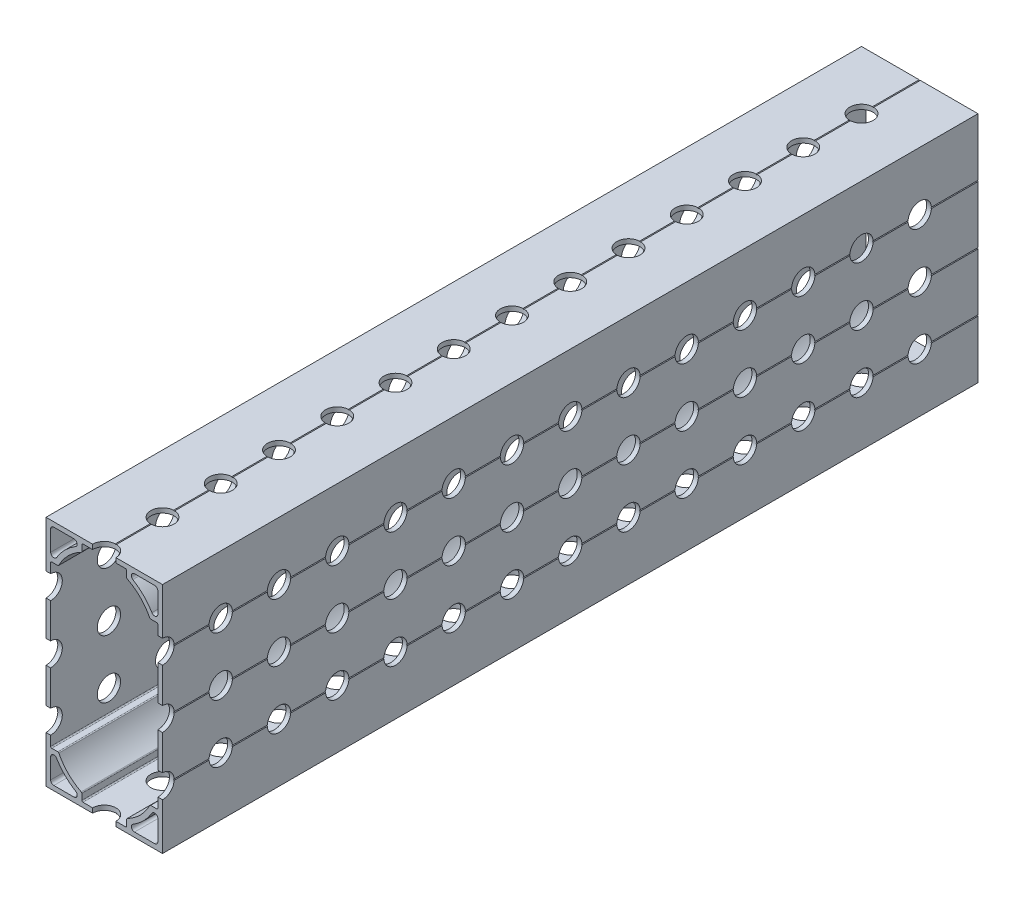
SolidWorks part; units mm, degrees
material "6061 Alloy"
ref_plane "Front Plane" through (0, 0, 0) normal (0, 0, 1) x (1, 0, 0)
ref_plane "Top Plane" through (0, 0, 0) normal (0, 1, 0) x (1, 0, 0)
ref_plane "Right Plane" through (0, 0, 0) normal (1, 0, 0) x (0, 0, -1)
other "Configuration Table"
sketch "Sketch3" plane through (0, 0, 0) normal (0, 0, 1) x (1, 0, 0)
  line L0 (0, 12.7) -> (0, -12.7) construction
  line L1 (12.7, -25.4) -> (0.127, -25.4)
  line L2 (12.7, -12.827) -> (12.7, -25.4)
  line L3 (12.573, -12.7) -> (12.7, -12.827)
  line L4 (-10.9924, -24.384) -> (-6.5971, -24.384)
  line L5 (-11.684, -19.2971) -> (-11.684, -23.6924)
  line L6 (12.7, -12.573) -> (12.573, -12.7)
  line L7 (12.7, -0.127) -> (12.7, -12.573)
  line L10 (12.573, 0) -> (12.7, -0.127)
  line L11 (0.127, -25.4) -> (0, -25.273)
  line L14 (11.684, 0) -> (11.684, -17.5895)
  line L15 (11.684, -17.5895) -> (9.979, -17.5895)
  line L18 (4.8895, -22.679) -> (4.8895, -24.384)
  line L19 (11.684, -19.2971) -> (11.684, -23.6924)
  line L20 (10.9924, -24.384) -> (6.5971, -24.384)
  line L21 (55, 0) -> (-55, 0) construction
  line L37 (12.573, 0) -> (12.7, 0.127)
  line L46 (-4.8895, -24.384) -> (4.8895, -24.384)
  line L47 (-4.8895, -22.679) -> (-4.8895, -24.384)
  line L48 (-11.684, -17.5895) -> (-9.979, -17.5895)
  line L49 (-11.684, 0) -> (-11.684, -17.5895)
  line L57 (-0.127, 25.4) -> (-12.7, 25.4)
  line L58 (-12.7, 12.827) -> (-12.7, 25.4)
  line L59 (-12.573, 12.7) -> (-12.7, 12.827)
  line L60 (-12.7, 12.573) -> (-12.573, 12.7)
  line L61 (-12.7, 0.127) -> (-12.7, 12.573)
  line L62 (-12.573, 0) -> (-12.7, 0.127)
  line L63 (-0.127, 25.4) -> (0, 25.273)
  line L64 (-11.684, 0) -> (-11.684, 17.5895)
  line L65 (-11.684, 17.5895) -> (-9.979, 17.5895)
  line L66 (-4.8895, 22.679) -> (-4.8895, 24.384)
  line L67 (-4.8895, 24.384) -> (4.8895, 24.384)
  line L69 (10.9924, 24.384) -> (6.5971, 24.384)
  line L70 (11.684, 19.2971) -> (11.684, 23.6924)
  line L71 (4.8895, 22.679) -> (4.8895, 24.384)
  line L72 (11.684, 17.5895) -> (9.979, 17.5895)
  line L73 (11.684, 0) -> (11.684, 17.5895)
  line L74 (0.127, 25.4) -> (0, 25.273)
  line L76 (12.7, 0.127) -> (12.7, 12.573)
  line L77 (12.7, 12.573) -> (12.573, 12.7)
  line L78 (-11.684, 19.2971) -> (-11.684, 23.6924)
  line L79 (-10.9924, 24.384) -> (-6.5971, 24.384)
  line L80 (12.573, 12.7) -> (12.7, 12.827)
  line L81 (12.7, 12.827) -> (12.7, 25.4)
  line L82 (12.7, 25.4) -> (0.127, 25.4)
  line L96 (-0.127, -25.4) -> (0, -25.273)
  line L118 (-12.573, 0) -> (-12.7, -0.127)
  line L119 (-12.7, -0.127) -> (-12.7, -12.573)
  line L120 (-12.7, -12.573) -> (-12.573, -12.7)
  line L121 (-12.573, -12.7) -> (-12.7, -12.827)
  line L122 (-12.7, -12.827) -> (-12.7, -25.4)
  line L123 (-12.7, -25.4) -> (-0.127, -25.4)
  arc A0 (9.979, -17.5895) -> (4.8895, -22.679) centre (0, -12.7) cw
  arc A1 (6.5971, -24.384) -> (6.2412, -23.0994) centre (6.5971, -23.6924) cw
  arc A2 (10.3994, -18.9412) -> (6.2412, -23.0994) centre (0, -12.7) cw
  arc A3 (10.3994, -18.9412) -> (11.684, -19.2971) centre (10.9924, -19.2971) cw
  arc A4 (11.684, -23.6924) -> (10.9924, -24.384) centre (10.9924, -23.6924) cw
  arc A10 (-11.684, -23.6924) -> (-10.9924, -24.384) centre (-10.9924, -23.6924) ccw
  arc A11 (-10.3994, -18.9412) -> (-11.684, -19.2971) centre (-10.9924, -19.2971) ccw
  arc A12 (-10.3994, -18.9412) -> (-6.2412, -23.0994) centre (0, -12.7) ccw
  arc A14 (-6.5971, -24.384) -> (-6.2412, -23.0994) centre (-6.5971, -23.6924) ccw
  arc A24 (-9.979, 17.5895) -> (-4.8895, 22.679) centre (0, 12.7) cw
  arc A25 (-6.5971, 24.384) -> (-6.2412, 23.0994) centre (-6.5971, 23.6924) cw
  arc A30 (-10.3994, 18.9412) -> (-6.2412, 23.0994) centre (0, 12.7) cw
  arc A31 (-10.3994, 18.9412) -> (-11.684, 19.2971) centre (-10.9924, 19.2971) cw
  arc A32 (-11.684, 23.6924) -> (-10.9924, 24.384) centre (-10.9924, 23.6924) cw
  arc A33 (11.684, 23.6924) -> (10.9924, 24.384) centre (10.9924, 23.6924) ccw
  arc A34 (10.3994, 18.9412) -> (11.684, 19.2971) centre (10.9924, 19.2971) ccw
  arc A35 (10.3994, 18.9412) -> (6.2412, 23.0994) centre (0, 12.7) ccw
  arc A41 (6.5971, 24.384) -> (6.2412, 23.0994) centre (6.5971, 23.6924) ccw
  arc A42 (9.979, 17.5895) -> (4.8895, 22.679) centre (0, 12.7) ccw
  arc A46 (-9.979, -17.5895) -> (-4.8895, -22.679) centre (0, -12.7) ccw
  point P71 (0, -24.384)
  point P104 (-11.684, -8.7948)
  point P108 (11.684, -8.7948)
  point P130 (11.684, 8.7948)
  point P131 (-11.684, 8.7948)
  point P132 (0, 24.384)
  dimension "D4" = 0.6916
  dimension "D7" = 11.1125
  dimension "D14" = 12.1285
  dimension "D1" = 25.4
  dimension "D2" = 12.573
  dimension "D3" = 5.7785
  dimension "D5" = 12.7
  dimension "D6" = 4.8895
  dimension "D8" = 1.016
  dimension "D9" = 135
  dimension "D10" = 0.127
  dimension "D11" = 1.016
  dimension "D12" = 135
  dimension "D13" = 135
extrude "Boss-Extrude1" add sketch "Sketch3" along normal blind 177.8 contours L48 A46 L47 L46 L18 A0 L15 L14 L73 L72 A42 L71 L67 L66 A24 L65 L64 L49 | A32 L78 A31 A30 A25 L79 | L69 A41 A35 A34 L70 A33 | L4 A14 A12 A11 L5 A10 | A4 L19 A3 A2 A1 L20 | L57 L58 L59 L60 L61 L62 L118 L119 L120 L121 L122 L123 L96 L11 L1 L2 L3 L6 L7 L10 L37 L76 L77 L80 L81 L82 L74 L63 region at (-9.5535, -22.2535, 0) region at (0, 0, 0) region at (9.5535, -22.2535, 0) region at (9.5535, 22.2535, 0) region at (-9.5535, 22.2535, 0)
sketch "Sketch2" plane through (25.4, 25.4, 0) normal (0, -1, 0) x (0, 0, 1)
  line L2 (177.8, 25.4) -> (0, 25.4) construction
  line L3 (0, 12.7) -> (0, 25.273) construction
  circle A0 centre (12.7, 25.4) radius 2.54
  dimension "D1" = 5.08
  dimension "D2" = 12.7
extrude "Cut-Extrude1" cut sketch "Sketch2" along normal through all
pattern_linear "LPattern1" count 95 spacing 12.7 along (0, 0, 1) of "Cut-Extrude1"
fillet "Fillet1" radius 0.254 16 edges at (9.979, 17.5895, 88.9) (11.684, 17.5895, 88.9) (4.8895, 22.679, 88.9) (4.8895, 24.384, 88.9) (11.684, -17.5895, 88.9) (9.979, -17.5895, 88.9) (4.8895, -22.679, 88.9) (4.8895, -24.384, 88.9) (-4.8895, -22.679, 88.9) (-4.8895, -24.384, 88.9) (-9.979, -17.5895, 88.9) (-11.684, -17.5895, 88.9) (-4.8895, 24.384, 88.9) (-4.8895, 22.679, 88.9) (-11.684, 17.5895, 88.9) (-9.979, 17.5895, 88.9)
sketch "Sketch4" plane through (12.7, 0, 0) normal (1, 0, 0) x (0, 0, -1)
  line L0 (-177.8, 12.7) -> (0, 12.7) construction
  line L1 (-177.8, 0) -> (0, 0) construction
  line L2 (-177.8, -12.7) -> (0, -12.7) construction
  line L3 (0, 12.827) -> (0, 25.4) construction
  circle A0 centre (-12.7, 12.7) radius 2.54
  circle A1 centre (-12.7, 0) radius 2.54
  circle A2 centre (-12.7, -12.7) radius 2.54
  dimension "D1" = 2.54
  dimension "D2" = 12.7
extrude "Cut-Extrude2" cut sketch "Sketch4" against normal through all
pattern_linear "LPattern2" count 94 spacing 12.7 along (0, 0, 1) of "Cut-Extrude2"
equation "\"Length\"= 7"
equation "\"D1@Boss-Extrude1\"=\"Length\""
